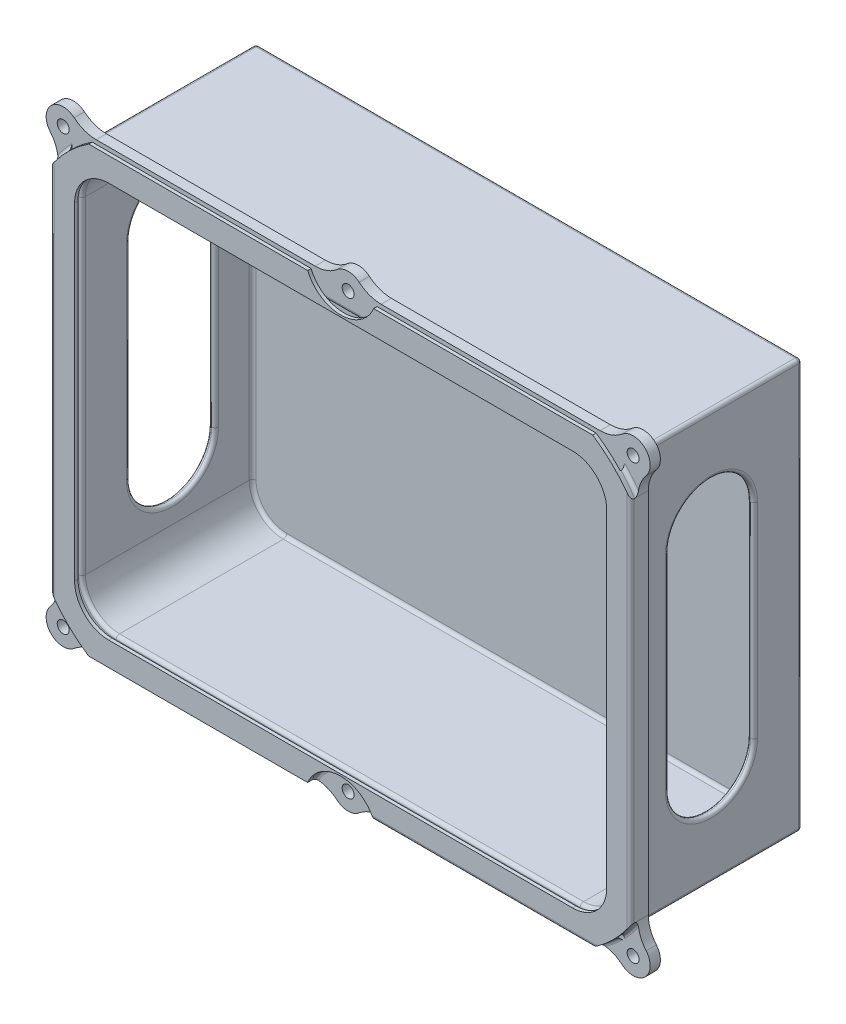
SolidWorks part; units mm, degrees
ref_plane "Front Plane" through (0, 0, 0) normal (0, 0, 1) x (1, 0, 0)
ref_plane "Top Plane" through (0, 0, 0) normal (0, 1, 0) x (1, 0, 0)
ref_plane "Right Plane" through (0, 0, 0) normal (1, 0, 0) x (0, 0, -1)
sketch "Sketch1" plane through (0, 0, 0) normal (0, 0, 1) x (1, 0, 0)
  line L1 (-44, 54) -> (44, 54)
  line L2 (-44, 54) -> (-44, -54)
  line L3 (-44, -54) -> (44, -54)
  line L4 (44, 54) -> (44, -54)
  line L5 (-44, 54) -> (44, -54) construction
  line L6 (-44, -54) -> (44, 54) construction
  point P0 (0, 0)
  dimension "D1" = 108
  dimension "D2" = 88
sketch "Sketch2" plane through (0, 0, 0) normal (0, 0, 1) x (1, 0, 0)
  line L1 (-80, 60) -> (80, 60)
  line L2 (-80, 60) -> (-80, -60)
  line L3 (-80, -60) -> (80, -60)
  line L4 (80, 60) -> (80, -60)
  line L5 (-80, 60) -> (80, -60) construction
  line L6 (-80, -60) -> (80, 60) construction
  point P0 (0, 0)
  dimension "D1" = 120
  dimension "D2" = 160
extrude "Boss-Extrude1" add sketch "Sketch2" along normal blind 3
sketch "Sketch3" plane through (0, 0, 3) normal (0, 0, 1) x (1, 0, 0)
  line L1 (-80, 60) -> (80, 60)
  line L2 (-80, 60) -> (-80, -60)
  line L3 (-80, -60) -> (80, -60)
  line L4 (80, 60) -> (80, -60)
  line L5 (-80, 60) -> (80, -60) construction
  line L6 (-80, -60) -> (80, 60) construction
  line L8 (-78, 58) -> (78, 58)
  line L9 (-78, 58) -> (-78, -58)
  line L10 (-78, -58) -> (78, -58)
  line L11 (78, 58) -> (78, -58)
  line L12 (-78, 58) -> (78, -58) construction
  line L13 (-78, -58) -> (78, 58) construction
  point P0 (0, 0)
  dimension "D1" = 2
  dimension "D2" = 2
extrude "Boss-Extrude2" add sketch "Sketch3" along normal blind 50
sketch "Sketch5" plane through (0, 0, 0) normal (1, 0, 0) x (0, 0, -1)
  line L0 (-53, -60) -> (0, 60) construction
  line L1 (-26.5, -30) -> (-26.5, 0) construction
  line L2 (0, 0) -> (-53, 0) construction
  line L3 (0, -60) -> (0, 60) construction
  line L4 (-53, -60) -> (-53, 60) construction
  line L5 (-53, 0) -> (0, -60) construction
  line L6 (-39, 30) -> (-39, -30)
  line L7 (-14, -30) -> (-14, 30)
  circle A0 centre (-26.5, -30) radius 12.5
  circle A1 centre (-26.5, 30) radius 12.5
  dimension "D1" = 25
extrude "Cut-Extrude1" cut sketch "Sketch5" against normal through all both and the other way through all contours A0 | L7 A1 L6 A0 | A1 region at (0, 0, 26.5) region at (0, 30, 26.5) region at (0, -30, 26.5)
sketch "Sketch6" plane through (0, 0, 53) normal (0, 0, 1) x (1, 0, 0)
  line L0 (80, -60) -> (80, 60) construction
  line L1 (-85, -65) -> (85, -65)
  line L2 (-85, -65) -> (-85, 65)
  line L3 (-85, 65) -> (85, 65)
  line L4 (85, -65) -> (85, 65)
  line L5 (-85, -65) -> (85, 65) construction
  line L6 (-85, 65) -> (85, -65) construction
  line L7 (-78, -58) -> (78, -58)
  line L8 (-78, -58) -> (-78, 58)
  line L9 (-78, 58) -> (78, 58)
  line L10 (78, -58) -> (78, 58)
  line L11 (-78, -58) -> (78, 58) construction
  line L12 (-78, 58) -> (78, -58) construction
  line L13 (80, 60) -> (-80, 60) construction
  point P0 (0, 0)
  point P6 (0, 0)
  dimension "D1" = 5
  dimension "D2" = 5
extrude "Boss-Extrude3" add sketch "Sketch6" against normal blind 3
sketch "Sketch8" plane through (0, 0, 53) normal (0, 0, 1) x (1, 0, 0)
  line L0 (85.985, 65.985) -> (85, 65) construction
  line L1 (81.086, 61.086) -> (84.4321, 60.1895)
  line L2 (84.4321, 60.1895) -> (86.8816, 62.639)
  line L3 (86.8816, 62.639) -> (85.985, 65.985)
  line L4 (85.985, 65.985) -> (82.639, 66.8816)
  line L5 (82.639, 66.8816) -> (80.1895, 64.4321)
  line L6 (80.1895, 64.4321) -> (81.086, 61.086)
  line L7 (85, 65) -> (80, 60) construction
  line L8 (0, 0) -> (85, 0) construction
  line L9 (85, -65) -> (85, 65) construction
  line L10 (0, 0) -> (0, 65) construction
  line L11 (85, 65) -> (-85, 65) construction
  line L12 (83.5355, 68.5355) -> (0, 68.5355) construction
  line L13 (-85, 65) -> (-80, 60) construction
  line L14 (-3.4641, 63.5355) -> (-1.7321, 60.5355)
  line L15 (-1.7321, 60.5355) -> (1.7321, 60.5355)
  line L16 (1.7321, 60.5355) -> (3.4641, 63.5355)
  line L17 (3.4641, 63.5355) -> (1.7321, 66.5355)
  line L18 (1.7321, 66.5355) -> (-1.7321, 66.5355)
  line L19 (-1.7321, 66.5355) -> (-3.4641, 63.5355)
  line L20 (-85.985, 65.985) -> (-85, 65) construction
  line L21 (-80.1895, 64.4321) -> (-81.086, 61.086)
  line L22 (-82.639, 66.8816) -> (-80.1895, 64.4321)
  line L23 (-85.985, 65.985) -> (-82.639, 66.8816)
  line L24 (-86.8816, 62.639) -> (-85.985, 65.985)
  line L25 (-84.4321, 60.1895) -> (-86.8816, 62.639)
  line L26 (-81.086, 61.086) -> (-84.4321, 60.1895)
  line L27 (-85.985, -65.985) -> (-85, -65) construction
  line L28 (-85, -65) -> (-80, -60) construction
  line L29 (-81.086, -61.086) -> (-84.4321, -60.1895)
  line L30 (-84.4321, -60.1895) -> (-86.8816, -62.639)
  line L31 (-86.8816, -62.639) -> (-85.985, -65.985)
  line L32 (-85.985, -65.985) -> (-82.639, -66.8816)
  line L33 (-82.639, -66.8816) -> (-80.1895, -64.4321)
  line L34 (-80.1895, -64.4321) -> (-81.086, -61.086)
  line L35 (85, -65) -> (80, -60) construction
  line L36 (85.985, -65.985) -> (85, -65) construction
  line L37 (80.1895, -64.4321) -> (81.086, -61.086)
  line L38 (82.639, -66.8816) -> (80.1895, -64.4321)
  line L39 (85.985, -65.985) -> (82.639, -66.8816)
  line L40 (86.8816, -62.639) -> (85.985, -65.985)
  line L41 (84.4321, -60.1895) -> (86.8816, -62.639)
  line L42 (81.086, -61.086) -> (84.4321, -60.1895)
  line L43 (-1.7321, -66.5355) -> (-3.4641, -63.5355)
  line L44 (1.7321, -66.5355) -> (-1.7321, -66.5355)
  line L45 (3.4641, -63.5355) -> (1.7321, -66.5355)
  line L46 (1.7321, -60.5355) -> (3.4641, -63.5355)
  line L47 (-1.7321, -60.5355) -> (1.7321, -60.5355)
  line L48 (-3.4641, -63.5355) -> (-1.7321, -60.5355)
  circle A0 centre (83.5355, 63.5355) radius 3 construction
  circle A1 centre (83.5355, 63.5355) radius 5
  circle A2 centre (0, 63.5355) radius 5
  circle A3 centre (0, 63.5355) radius 3 construction
  circle A4 centre (-83.5355, 63.5355) radius 3 construction
  circle A5 centre (-83.5355, 63.5355) radius 5
  circle A6 centre (-83.5355, -63.5355) radius 3 construction
  circle A7 centre (-83.5355, -63.5355) radius 5
  circle A8 centre (83.5355, -63.5355) radius 3 construction
  circle A9 centre (83.5355, -63.5355) radius 5
  circle A10 centre (0, -63.5355) radius 3 construction
  circle A11 centre (0, -63.5355) radius 5
  line M24 (85, -65) -> (85, 65)
  line M25 (85, 65) -> (-85, 65)
  line M26 (-85, 65) -> (-85, -65)
  line M27 (-85, -65) -> (85, -65)
  dimension "D1" = 6
  dimension "D2" = 10
  dimension "D3" = 10
  dimension "D4" = 6
extrude "Boss-Extrude4" add sketch "Sketch8" against normal blind 3 contours L4 L5 L2 L3 M25 M24 | A1 L5 L4 L3 L2 M24 M25 | A9 L41 L40 L39 L38 M24 M27 | L41 L38 L39 L40 M24 M27 | L32 L33 L30 L31 M27 M26 | A7 L33 L32 L31 L30 M26 M27 | L45 L43 L44 M27 | A11 L45 L44 L43 M27 | A2 L19 L18 L17 M25 | L18 L19 L17 M25 | A5 L25 L24 L23 L22 M26 M25 | L25 L22 L23 L24 M26 M25 region at (85.0866, 62.8787, 53) region at (86.0386, 61.6004, 53) region at (87.4444, -60.6448, 53) region at (0, 66.7453, 53) region at (85.8796, -61.7594, 53) region at (0, 65.7156, 53) region at (0, -66.7453, 53) region at (-79.7561, 65.1383, 53) region at (0, -65.7156, 53) region at (-82.8787, 65.0866, 53) region at (-86.9733, -66.9733, 53) region at (-81.7594, -65.8796, 53)
sketch "Sketch9" plane through (0, 0, 50) normal (0, 0, -1) x (-1, 0, 0)
  circle A0 centre (-83.5355, 63.5355) radius 1.75
  circle A1 centre (-83.5355, -63.5355) radius 1.75
  circle A2 centre (0, -63.5355) radius 1.75
  circle A3 centre (83.5355, -63.5355) radius 1.75
  circle A4 centre (83.5355, 63.5355) radius 1.75
  circle A5 centre (0, 63.5355) radius 1.75
  arc A6 (4.7807, 65) -> (-4.7807, 65) centre (0, 63.5355) ccw construction
  arc A7 (-78.7548, 65) -> (-85, 58.7548) centre (-83.5355, 63.5355) ccw construction
  arc A8 (-85, -58.7548) -> (-78.7548, -65) centre (-83.5355, -63.5355) ccw construction
  arc A9 (78.7548, -65) -> (85, -58.7548) centre (83.5355, -63.5355) ccw construction
  arc A10 (85, 58.7548) -> (78.7548, 65) centre (83.5355, 63.5355) ccw construction
  arc A11 (-4.7807, -65) -> (4.7807, -65) centre (0, -63.5355) ccw construction
  dimension "D1" = 3.5
extrude "Cut-Extrude2" cut sketch "Sketch9" against normal through all
fillet "Fillet1" radius 10 12 edges at (-4.7807, -65, 51.5) (4.7807, -65, 51.5) (78.7548, -65, 51.5) (85, -58.7548, 51.5) (85, 58.7548, 51.5) (78.7548, 65, 51.5) (4.7807, 65, 51.5) (-4.7807, 65, 51.5) (-78.7548, 65, 51.5) (-85, -58.7548, 51.5) (-78.7548, -65, 51.5) (-85, 58.7548, 51.5)
sketch "Sketch12" plane through (0, 0, 53) normal (0, 0, 1) x (1, 0, 0)
  line L0 (-85, 53.8626) -> (-85, -53.8626) construction
  line L1 (78, -58) -> (-78, -58)
  line L2 (78, -58) -> (78, 58)
  line L3 (78, 58) -> (-78, 58)
  line L4 (-78, -58) -> (-78, 58)
  line L5 (78, -58) -> (-78, 58) construction
  line L6 (78, 58) -> (-78, -58) construction
  line L7 (85, -65) -> (-85, -65)
  line L8 (85, -65) -> (85, 65)
  line L9 (85, 65) -> (-85, 65)
  line L10 (-85, -65) -> (-85, 65)
  line L11 (85, -65) -> (-85, 65) construction
  line L12 (85, 65) -> (-85, -65) construction
  line L13 (-9.673, 65) -> (-73.8626, 65) construction
  line L14 (0, 0) -> (0, 58) construction
  line L15 (0, 0) -> (78, 0) construction
  arc A1 (-73.8626, 65) -> (-85, 53.8626) centre (-52.4517, 32.4517) ccw
  circle A2 centre (-83.5355, 63.5355) radius 5
  arc A3 (-80.3112, 67.357) -> (-87.357, 60.3112) centre (-83.5355, 63.5355) ccw construction
  arc A4 (73.8626, 65) -> (85, 53.8626) centre (52.4517, 32.4517) cw
  arc A5 (-73.8626, -65) -> (-85, -53.8626) centre (-52.4517, -32.4517) cw
  arc A6 (73.8626, -65) -> (85, -53.8626) centre (52.4517, -32.4517) ccw
  circle A7 centre (0, 63.5355) radius 5
  arc A9 (3.2243, 67.357) -> (-3.2243, 67.357) centre (0, 63.5355) ccw construction
  circle A10 centre (0, -63.5355) radius 5
  arc A11 (-3.2243, -67.357) -> (3.2243, -67.357) centre (0, -63.5355) ccw construction
  arc A12 (-9.673, -65) -> (9.673, -65) centre (0, -69.0047) cw
  arc A13 (-9.673, 65) -> (9.673, 65) centre (0, 69.0047) ccw
  point P0 (0, 0)
  point P6 (0, 0)
  circle M13 centre (0, -63.5355) radius 1.75
  circle M16 centre (0, 63.5355) radius 1.75
  line M18 (-85, 53.8626) -> (-85, -53.8626)
  line M22 (-73.8626, -65) -> (-9.673, -65)
  line M26 (9.673, -65) -> (73.8626, -65)
  line M30 (85, -53.8626) -> (85, 53.8626)
  line M34 (73.8626, 65) -> (9.673, 65)
  line M38 (-9.673, 65) -> (-73.8626, 65)
  line M42 (-78, 58) -> (78, 58)
  line M43 (78, 58) -> (78, -58)
  line M44 (78, -58) -> (-78, -58)
  line M45 (-78, -58) -> (-78, 58)
extrude "Boss-Extrude5" add sketch "Sketch12" along normal blind 2.2 contours A6 A4 L9 A1 A5 L7 M26 M30 M34 M16 M38 M18 M22 M13 M45 M42 M43 M44 region at (41.7678, -62.8599, 53)
fillet "Fillet3" radius 10 4 edges at (78, 58, 29.1) (78, -58, 29.1) (-78, -58, 29.1) (-78, 58, 29.1)
sketch "Sketch13" plane through (0, 0, 53) normal (0, 0, 1) x (1, 0, 0)
  line L0 (78, 48) -> (78, -48) construction
  line L1 (-81, -61) -> (81, -61)
  line L2 (-81, -61) -> (-81, 65)
  line L3 (-81, 65) -> (81, 65)
  line L4 (81, -61) -> (81, 65)
  line L5 (-78, 48) -> (-78, -48) construction
  line L6 (68, -58) -> (-68, -58) construction
  line L7 (73.8626, 65) -> (9.673, 65) construction
  dimension "D1" = 3
  dimension "D2" = 3
  dimension "D3" = 3
extrude "Cut-Extrude3" cut sketch "Sketch13" along normal blind 1.2
fillet "Fillet4" radius 1 55 edges at (-75.0711, -55.0711, 53) (0, -58, 53) (75.0711, -55.0711, 53) (78, 0, 53) (75.0711, 55.0711, 53) (0, 58, 53) (-75.0711, 55.0711, 53) (0, 60, 50) (-80, 60, 25) (-80, 0, 50) (-80, -60, 25) (0, -60, 50) (80, -60, 25) (80, 0, 50) (80, 60, 25) (0, 60, 0) (-80, 0, 0) (0, -60, 0) (80, 0, 0) (80, -42.5, 26.5) (78, -42.5, 26.5) (-80, -42.5, 26.5) (-78, -42.5, 26.5) (75.0711, -55.0711, 3) (0, -58, 3) (-75.0711, -55.0711, 3) (-78, 0, 3) (-75.0711, 55.0711, 3) (0, 58, 3) (75.0711, 55.0711, 3) (78, 0, 3) (83.1062, 56.4958, 53) (83.1062, -56.4958, 53) (76.4958, -63.1062, 53) (8.4503, -62.8244, 53) (-8.4503, -62.8244, 53) (-76.4958, -63.1062, 53) (-83.1062, -56.4958, 53) (-83.1062, 56.4958, 53) (-78, 0, 53) (41.7678, -65, 55.2) (85, 0, 55.2) (-85, 0, 55.2) (78, 0, 14) (78, 42.5, 26.5) (78, 0, 39) (-78, 0, 39) (-78, 42.5, 26.5) (-78, 0, 14) (-80, 42.5, 26.5) (-80, 0, 14) (-80, 0, 39) (80, 42.5, 26.5) (80, 0, 39) (80, 0, 14)
